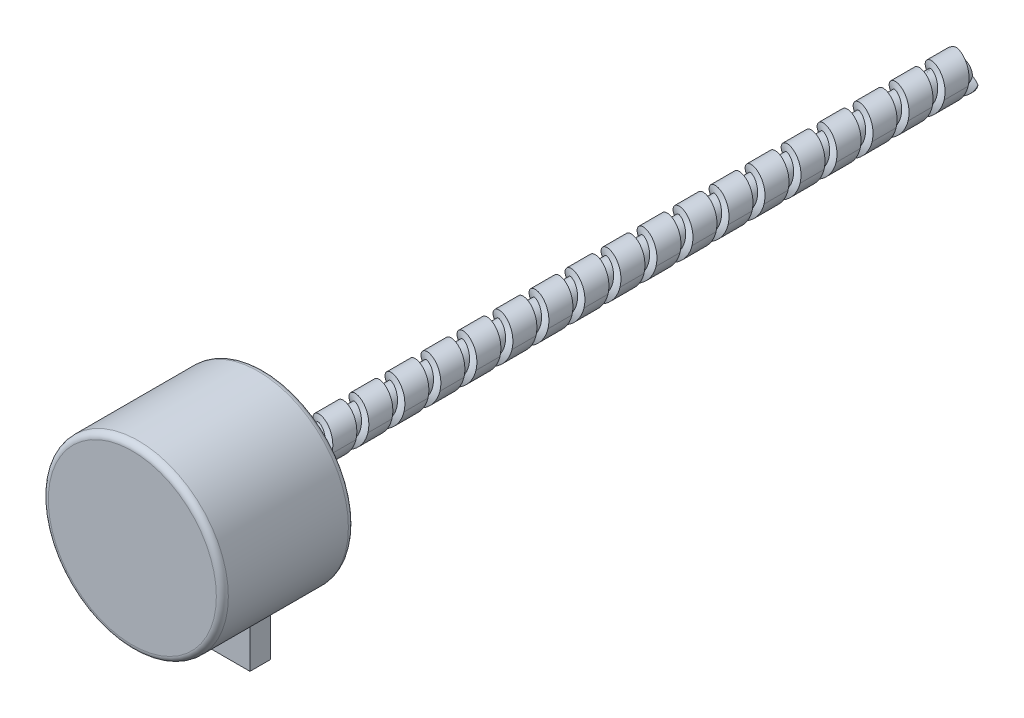
SolidWorks part; units mm, degrees
material "1023 碳钢板 (SS)"
ref_plane "前视基准面" through (0, 0, 0) normal (0, 0, 1) x (1, 0, 0)
ref_plane "上视基准面" through (0, 0, 0) normal (0, 1, 0) x (1, 0, 0)
ref_plane "右视基准面" through (0, 0, 0) normal (1, 0, 0) x (0, 0, -1)
other "Configuration Table"
sketch "草图1" plane through (0, 0, 0) normal (0, 0, 1) x (1, 0, 0)
  circle A0 centre (0, 0) radius 7.5
  dimension "D1" = 15
extrude "凸台-拉伸1" add sketch "草图1" along normal blind 11
fillet "圆角1" radius 0.5 2 edges at (7.5, 0, 0) (7.5, 0, 11)
sketch "草图2" plane through (0, 0, 0) normal (0, 0, -1) x (-1, 0, 0)
  circle A0 centre (0, 0) radius 1.5
  dimension "D1" = 3
extrude "凸台-拉伸2" add sketch "草图2" along normal blind 58
cosmetic thread "装饰螺纹线1" [suppressed] parameters "D2"=0.3
sketch "草图5" plane through (0, 0, -58) normal (0, 0, -1) x (-1, 0, 0)
  circle A0 centre (0, 0) radius 1.5
curve "螺旋线/涡状线1" pitch 3 height 57 radius 1.5 left hand yes centre (0, 0, -58) axis (0, 0, 1) start towards (0.7071, 0.7071, 0)
sketch "草图6" plane through (0, 0, 0) normal (0, 1, 0) x (1, 0, 0)
  line L0 (1.5, 54.125) -> (1.5, 55.125)
  line L1 (1.5, 55.125) -> (1, 54.975)
  line L2 (1, 54.975) -> (1, 54.275)
  line L3 (1, 54.275) -> (1.5, 54.125)
  line L4 (-0.7092, 54.625) -> (3.8675, 54.625) construction
  point P7 (1.5, 54.625)
  dimension "D1" = 1
  dimension "D2" = 0.7
  dimension "D3" = 0.5
sweep "切除-扫描1" cut profiles "草图6" path "螺旋线/涡状线1" align with end faces yes
sketch "草图7" plane through (0, 0, 0) normal (0, 1, 0) x (1, 0, 0)
  line L1 (4.1, -3.6) -> (-4.1, -3.6)
  line L2 (4.1, -3.6) -> (4.1, -5.3)
  line L3 (4.1, -5.3) -> (-4.1, -5.3)
  line L4 (-4.1, -3.6) -> (-4.1, -5.3)
  line L5 (4.1, -3.6) -> (-4.1, -5.3) construction
  line L6 (4.1, -5.3) -> (-4.1, -3.6) construction
  line L7 (7, 0) -> (-7, 0) construction
  point P0 (0, -4.45)
  point P7 (0, 0)
  dimension "D1" = 5.3
  dimension "D2" = 1.7
  dimension "D3" = 8.2
extrude "凸台-拉伸3" add sketch "草图7" against normal blind 9.7
